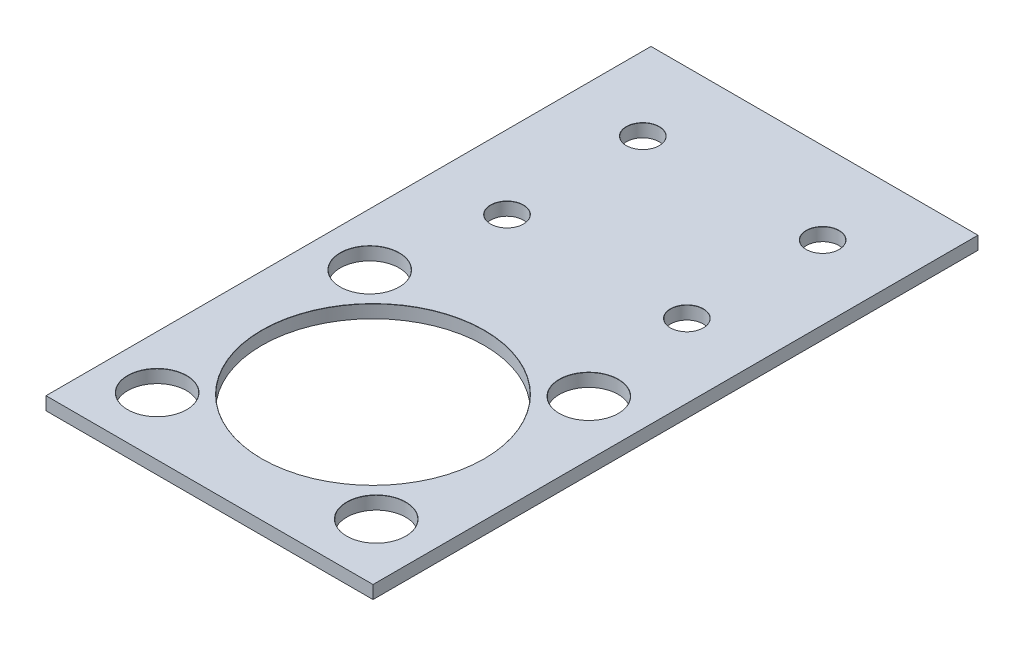
SolidWorks part; units mm, degrees
ref_plane "Front Plane" through (0, 0, 0) normal (0, 0, 1) x (1, 0, 0)
ref_plane "Top Plane" through (0, 0, 0) normal (0, 1, 0) x (1, 0, 0)
ref_plane "Right Plane" through (0, 0, 0) normal (1, 0, 0) x (0, 0, -1)
sketch "Sketch1" plane through (0, 0, 0) normal (0, 1, 0) x (1, 0, 0)
  line L1 (-27.5, 45) -> (22.5, 45)
  line L2 (-27.5, 45) -> (-27.5, -47.5)
  line L3 (-27.5, -47.5) -> (22.5, -47.5)
  line L4 (22.5, 45) -> (22.5, -47.5)
  line L30 (-27.5, 29.49) -> (-27.5, 34.99)
  line L31 (-27.5, 8.99) -> (-27.5, 14.49)
  line L32 (22.5, -1.25) -> (-2.5, -1.25) construction
  circle A0 centre (-19.25, -38.5) radius 5
  circle A1 centre (14.25, -38.5) radius 5
  circle A2 centre (14.25, -6) radius 5
  circle A3 centre (-19.25, -6) radius 5
  circle A6 centre (-16.25, 32.5) radius 2.5
  circle A7 centre (-16.25, 11.74) radius 2.5
  circle A8 centre (11.25, 32.5) radius 2.5
  circle A9 centre (11.25, 11.74) radius 2.5
  circle A10 centre (-2.5, -22.25) radius 17.1
  point P0 (0, 0)
  point P41 (-16.25, 32.5)
  point P45 (-16.25, 11.74)
  point P47 (11.25, 32.5)
  point P51 (11.25, 11.74)
  dimension "D15" = 11.25
  dimension "D16" = 11.25
  dimension "D14" = 32.5
  dimension "D17" = 25.25
  dimension "D19" = 33.26
  dimension "D1" = 50
  dimension "D2" = 92.5
  dimension "D3" = 12.5
  dimension "D4" = 12.5
  dimension "D5" = 11.25
  dimension "D6" = 11.25
  dimension "D7" = 8.25
  dimension "D8" = 8.25
  dimension "D9" = 8.25
  dimension "D10" = 8.25
  dimension "D11" = 32.5
  dimension "D12" = 9
  dimension "D13" = 9
  dimension "D18" = 25
  dimension "D20" = 33.26
sketch "Sketch2" plane through (0, 0, 0) normal (0, 1, 0) x (1, 0, 0)
  line L1 (-27.5, 45) -> (22.5, 45)
  line L2 (-27.5, 45) -> (-27.5, -47.5)
  line L3 (-27.5, -47.5) -> (22.5, -47.5)
  line L4 (22.5, 45) -> (22.5, -47.5)
base flange "Base-Flange1" sketch "Sketch2" thickness 2 reverse thickness direction no parameters "D1"=0.7366
hole_wizard "Tap Drill for M6 Tap1" positions "Sketch1" profile "Sketch8" hole size "M6" standard "ISO"
sketch "Sketch8" plane through (11.25, 0, -11.74) normal (1, 0, 0) x (0, 0, 1)
  line L0 (0, 0) -> (0, 2)
  line L1 (0, 2) -> (2.5, 2)
  line L2 (2.5, 2) -> (2.5, 0.025)
  line L3 (2.5, 0.025) -> (2.525, 0)
  line L5 (2.525, 0) -> (0, 0)
  line L6 (-2.5, 0.025) -> (-2.525, 0) construction
  line L11 (0, -6.35) -> (0, 107.95) construction
  dimension "Thru Hole Dia." = 5
  dimension "Thru Hole Depth" = 2
  dimension "Near C'Sink Dia." = 5.05
  dimension "Near C'Sink Angle" = 90
sketch "Sketch14" plane through (0, 0, 0) normal (0, 1, 0) x (1, 0, 0)
  line L1 (-27.6671, 44.9127) -> (22.3329, 44.9127)
  line L2 (-27.6671, 44.9127) -> (-27.6671, -47.5873)
  line L3 (-27.6671, -47.5873) -> (22.3329, -47.5873)
  line L4 (22.3329, 44.9127) -> (22.3329, -47.5873)
  line L30 (-27.6671, 29.4027) -> (-27.6671, 34.9027)
  line L31 (-27.6671, 8.9027) -> (-27.6671, 14.4027)
  circle A0 centre (-19.4171, -38.5873) radius 5
  circle A1 centre (14.0829, -38.5873) radius 5
  circle A2 centre (14.0829, -6.0873) radius 5
  circle A3 centre (-19.4171, -6.0873) radius 5
  circle A6 centre (-16.4171, 32.4127) radius 2.5
  circle A7 centre (-16.4171, 11.6527) radius 2.5
  circle A8 centre (11.0829, 32.4127) radius 2.5
  circle A9 centre (11.0829, 11.6527) radius 2.5
  circle A10 centre (-2.6671, -22.3373) radius 17.1
  point P0 (-0.1671, -0.0873)
  point P26 (-19.4171, -38.5873)
  point P32 (14.0829, -38.5873)
  point P34 (14.0829, -6.0873)
  point P36 (-19.4171, -6.0873)
  point P41 (-16.4171, 32.4127)
  point P45 (-16.4171, 11.6527)
  point P47 (11.0829, 32.4127)
  point P51 (11.0829, 11.6527)
  dimension "D15" = 11.25
  dimension "D16" = 11.25
  dimension "D14" = 32.5
  dimension "D17" = 25.25
  dimension "D19" = 33.26
  dimension "D1" = 50
  dimension "D2" = 92.5
  dimension "D3" = 12.5
  dimension "D4" = 12.5
  dimension "D5" = 11.25
  dimension "D6" = 11.25
  dimension "D7" = 8.25
  dimension "D8" = 8.25
  dimension "D9" = 8.25
  dimension "D10" = 8.25
  dimension "D11" = 32.5
  dimension "D12" = 9
  dimension "D13" = 9
  dimension "D18" = 25
  dimension "D20" = 33.26
hole_wizard "Tap Drill for M10x1.0 Tap1" positions "Sketch14" profile "Sketch15" hole size "M10x1.0" standard "ISO"
sketch "Sketch15" plane through (-19.4171, 0, 6.0873) normal (1, 0, 0) x (0, 0, 1)
  line L0 (0, 0) -> (0, 2)
  line L1 (0, 2) -> (4.5, 2)
  line L2 (4.5, 2) -> (4.5, 0.025)
  line L3 (4.5, 0.025) -> (4.525, 0)
  line L5 (4.525, 0) -> (0, 0)
  line L6 (-4.5, 0.025) -> (-4.525, 0) construction
  line L11 (0, -6.35) -> (0, 107.95) construction
  dimension "Thru Hole Dia." = 9
  dimension "Thru Hole Depth" = 2
  dimension "Near C'Sink Dia." = 9.05
  dimension "Near C'Sink Angle" = 90
sketch "Sketch17" plane through (0, 0, 0) normal (0, 1, 0) x (1, 0, 0)
  line L1 (-27.4622, 44.7138) -> (22.5378, 44.7138)
  line L2 (-27.4622, 44.7138) -> (-27.4622, -47.7862)
  line L3 (-27.4622, -47.7862) -> (22.5378, -47.7862)
  line L4 (22.5378, 44.7138) -> (22.5378, -47.7862)
  line L30 (-27.4622, 29.2038) -> (-27.4622, 34.7038)
  line L31 (-27.4622, 8.7038) -> (-27.4622, 14.2038)
  circle A0 centre (-19.2122, -38.7862) radius 5
  circle A1 centre (14.2878, -38.7862) radius 5
  circle A2 centre (14.2878, -6.2862) radius 5
  circle A3 centre (-19.2122, -6.2862) radius 5
  circle A6 centre (-16.2122, 32.2138) radius 2.5
  circle A7 centre (-16.2122, 11.4538) radius 2.5
  circle A8 centre (11.2878, 32.2138) radius 2.5
  circle A9 centre (11.2878, 11.4538) radius 2.5
  circle A10 centre (-2.4622, -22.5362) radius 17.1
  point P0 (0.0378, -0.2862)
  point P26 (-19.2122, -38.7862)
  point P32 (14.2878, -38.7862)
  point P34 (14.2878, -6.2862)
  point P36 (-19.2122, -6.2862)
  point P41 (-16.2122, 32.2138)
  point P45 (-16.2122, 11.4538)
  point P47 (11.2878, 32.2138)
  point P51 (11.2878, 11.4538)
  point P55 (-2.6671, -22.3373)
  dimension "D15" = 11.25
  dimension "D16" = 11.25
  dimension "D14" = 32.5
  dimension "D17" = 25.25
  dimension "D19" = 33.26
  dimension "D1" = 50
  dimension "D2" = 92.5
  dimension "D3" = 12.5
  dimension "D4" = 12.5
  dimension "D5" = 11.25
  dimension "D6" = 11.25
  dimension "D7" = 8.25
  dimension "D8" = 8.25
  dimension "D9" = 8.25
  dimension "D10" = 8.25
  dimension "D11" = 32.5
  dimension "D12" = 9
  dimension "D13" = 9
  dimension "D18" = 25
  dimension "D20" = 33.26
hole_wizard "Tap Drill for M36x2.0 Tap1" positions "Sketch17" profile "Sketch18" hole size "M36x2.0" standard "ISO"
sketch "Sketch18" plane through (-2.6671, 0, 22.3373) normal (1, 0, 0) x (0, 0, 1)
  line L0 (0, 0) -> (0, 2)
  line L1 (0, 2) -> (17, 2)
  line L2 (17, 2) -> (17, 0.025)
  line L3 (17, 0.025) -> (17.025, 0)
  line L5 (17.025, 0) -> (0, 0)
  line L6 (-17, 0.025) -> (-17.025, 0) construction
  line L11 (0, -6.35) -> (0, 107.95) construction
  dimension "Thru Hole Dia." = 34
  dimension "Thru Hole Depth" = 2
  dimension "Near C'Sink Dia." = 34.05
  dimension "Near C'Sink Angle" = 90
sketch "Bend-Lines1" [suppressed] plane through (0, 0, 0) normal (0, 1, 0) x (1, 0, 0)
sketch "Bounding-Box1" [suppressed] plane through (0, 0, 0) normal (0, 1, 0) x (1, 0, 0)
sheet metal parameters "Sheet-Metal1" thickness 2 parameters "D1"=0.7366
flat pattern "Flat-Pattern1" [suppressed]
sketch "Bend-Lines2" plane through (0, 0, 0) normal (0, 1, 0) x (1, 0, 0)
sketch3d "Bounding-Box2" [suppressed]
  line L0 (-27.5, 45, 0) -> (-27.5, -47.5, 0) construction
  line L1 (22.5, 45, 0) -> (22.5, -47.5, 0) construction
  line L2 (-27.5, 45, 0) -> (22.5, 45, 0) construction
  line L3 (-27.5, -47.5, 0) -> (22.5, -47.5, 0) construction
sheet metal parameters "Sheet-Metal3" thickness 2 parameters "D1"=0.7366
flat pattern "Flat-Pattern1"
sketch "Bend-Lines2" plane through (0, 0, 0) normal (0, 1, 0) x (1, 0, 0)
sketch3d "Bounding-Box2" [suppressed]
  line L0 (-27.5, 45, 0) -> (-27.5, -47.5, 0) construction
  line L1 (22.5, 45, 0) -> (22.5, -47.5, 0) construction
  line L2 (-27.5, 45, 0) -> (22.5, 45, 0) construction
  line L3 (-27.5, -47.5, 0) -> (22.5, -47.5, 0) construction
sheet metal parameters "Sheet-Metal4" thickness 2 parameters "D1"=0.7366
flat pattern "Flat-Pattern1"
sketch "Bend-Lines2" plane through (0, 0, 0) normal (0, 1, 0) x (1, 0, 0)
sketch3d "Bounding-Box2" [suppressed]
  line L0 (-27.5, 45, 0) -> (-27.5, -47.5, 0) construction
  line L1 (22.5, 45, 0) -> (22.5, -47.5, 0) construction
  line L2 (-27.5, 45, 0) -> (22.5, 45, 0) construction
  line L3 (-27.5, -47.5, 0) -> (22.5, -47.5, 0) construction
sheet metal parameters "Sheet-Metal5" thickness 2 parameters "D1"=0.7366
flat pattern "Flat-Pattern1"
sketch "Bend-Lines2" plane through (0, 0, 0) normal (0, 1, 0) x (1, 0, 0)
sketch3d "Bounding-Box2" [suppressed]
  line L0 (-27.5, 45, 0) -> (-27.5, -47.5, 0) construction
  line L1 (22.5, 45, 0) -> (22.5, -47.5, 0) construction
  line L2 (-27.5, 45, 0) -> (22.5, 45, 0) construction
  line L3 (-27.5, -47.5, 0) -> (22.5, -47.5, 0) construction
